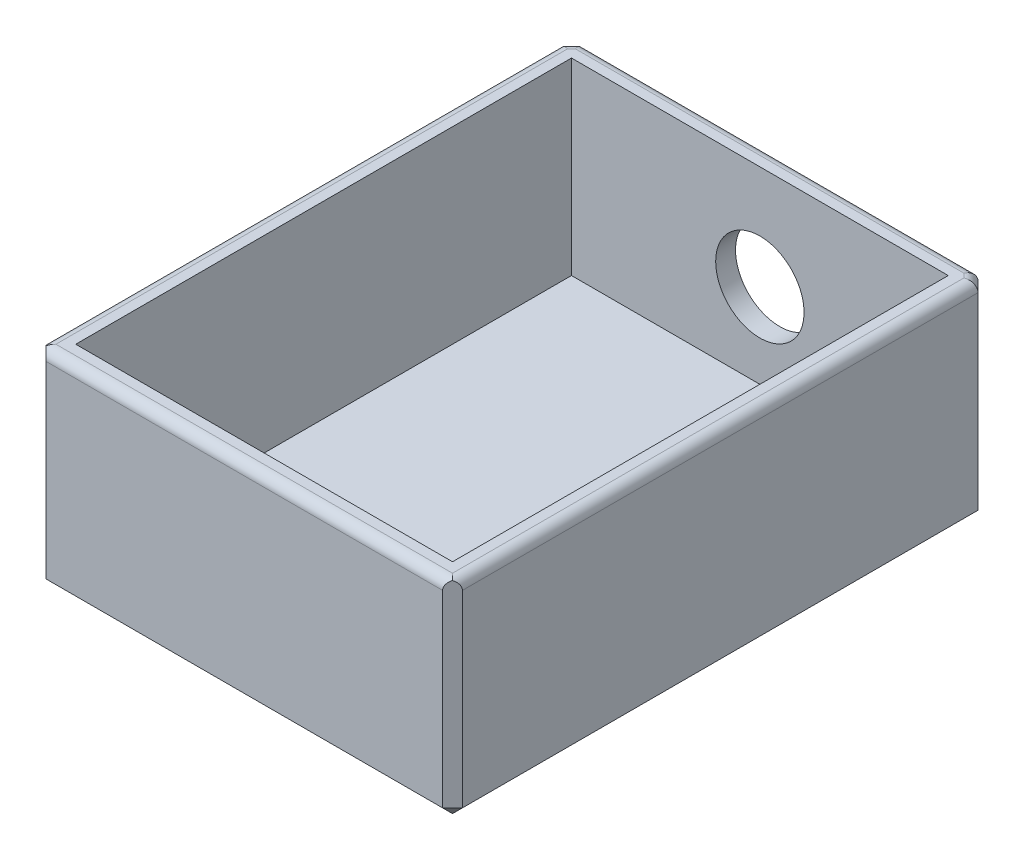
SolidWorks part; units mm, degrees
ref_plane "Front Plane" through (0, 0, 0) normal (0, 0, 1) x (1, 0, 0)
ref_plane "Top Plane" through (0, 0, 0) normal (0, 1, 0) x (1, 0, 0)
ref_plane "Right Plane" through (0, 0, 0) normal (1, 0, 0) x (0, 0, -1)
sketch "Sketch1" plane through (0, 0, 0) normal (0, 0, 1) x (1, 0, 0)
  line L0 (40, 2) -> (40, 21)
  line L1 (0, 0) -> (42, 0)
  line L2 (0, 0) -> (0, 21)
  line L3 (0, 21) -> (42, 21)
  line L4 (42, 0) -> (42, 21)
  line L5 (2, 2) -> (40, 2)
  line L6 (2, 2) -> (2, 21)
  dimension "D1" = 42
  dimension "D2" = 21
  dimension "D3" = 2
extrude "Boss-Extrude1" add sketch "Sketch1" along normal blind 50 contours L5 L6 L3 L2 L1 L4 L0 region at (40.4696, 11.5, 0)
extrude "Boss-Extrude2" add sketch "Sketch1<3>" against normal blind 2 contours L3 L4 L1 L2
sketch "Sketch1<3>" plane through (0, 0, 0) normal (0, 0, 1) x (1, 0, 0) same geometry as "Sketch1"
extrude "Boss-Extrude3" add sketch "Sketch1<4>" along normal blind 2 from surface contours L3 L4 L1 L2 starting at face at (21, 11, 50)
sketch "Sketch1<4>" plane through (0, 0, 0) normal (0, 0, 1) x (1, 0, 0) same geometry as "Sketch1"
sketch "Sketch2" plane through (0, 0, -2) normal (0, 0, -1) x (-1, 0, 0)
  line L0 (-42, 10.5) -> (0, 10.5) construction
  line L1 (-42, 0) -> (-42, 21) construction
  line L2 (0, 0) -> (0, 21) construction
  circle A0 centre (-21, 10.5) radius 4.4581
extrude "Cut-Extrude1" cut sketch "Sketch2" against normal blind 2
chamfer "Chamfer1" distance 1 angle 45 8 edges at (0, 10.5, 52) (42, 10.5, -2) (42, 10.5, 52) (21, 0, 52) (42, 0, 25) (0, 0, 25) (21, 0, -2) (0, 10.5, -2)
fillet "Fillet1" radius 1 6 edges at (21, 21, 52) (0, 21, 25) (42, 21, 25) (21, 21, -2) (0.5, 21, -1.5) (41.5, 21, -1.5)
